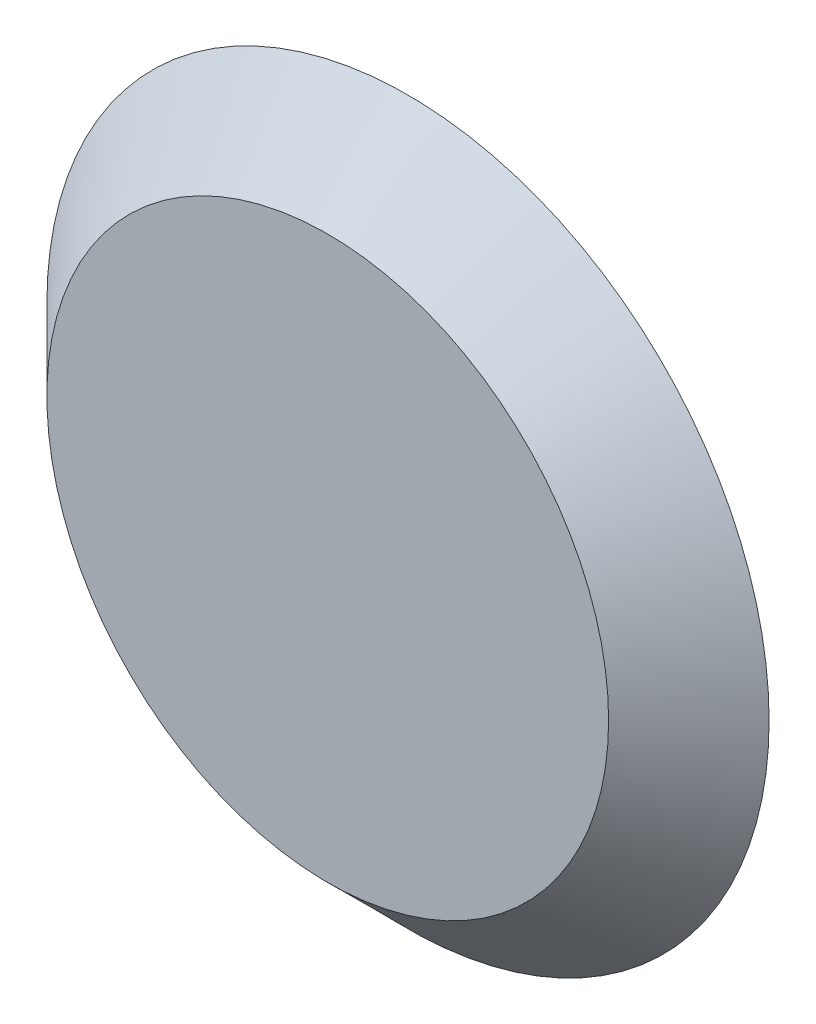
SolidWorks part; units mm, degrees
ref_plane "Front Plane" through (0, 0, 0) normal (0, 0, 1) x (1, 0, 0)
ref_plane "Top Plane" through (0, 0, 0) normal (0, 1, 0) x (1, 0, 0)
ref_plane "Right Plane" through (0, 0, 0) normal (1, 0, 0) x (0, 0, -1)
sketch "Sketch1" plane through (0, 0, 0) normal (0, 0, 1) x (1, 0, 0)
  circle A0 centre (0, 0) radius 4.5
  dimension "D1" = 9
extrude "Boss-Extrude1" add sketch "Sketch1" along normal blind 1
chamfer "Chamfer1" distance 1 angle 45 1 edges at (4.5, 0, 1)
